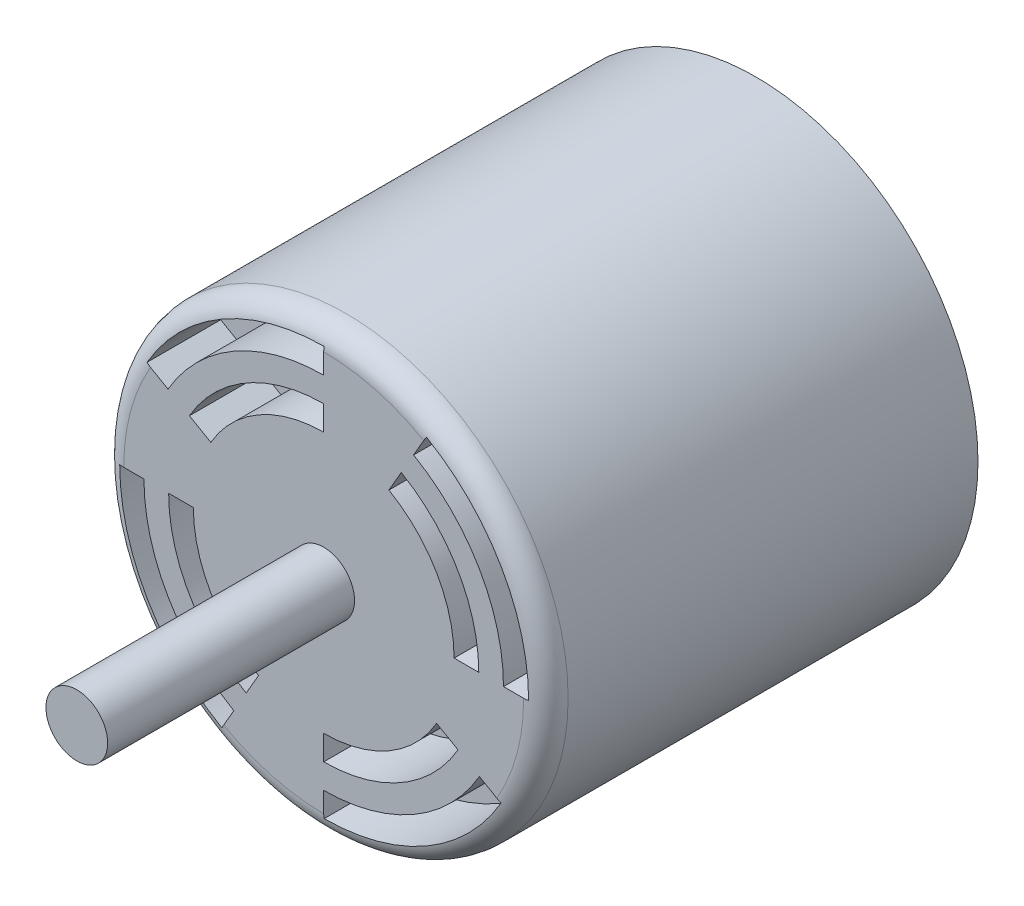
SolidWorks part; units mm, degrees
ref_plane "Front Plane" through (0, 0, 0) normal (0, 0, 1) x (1, 0, 0)
ref_plane "Top Plane" through (0, 0, 0) normal (0, 1, 0) x (1, 0, 0)
ref_plane "Right Plane" through (0, 0, 0) normal (1, 0, 0) x (0, 0, -1)
sketch "Sketch1" plane through (0, 0, 0) normal (0, 0, 1) x (1, 0, 0)
  circle A0 centre (0, 0) radius 22.86
  dimension "D1" = 45.72
extrude "Boss-Extrude1" add sketch "Sketch1" along normal blind 44.45
sketch "Sketch2" plane through (0, 0, 44.45) normal (0, 0, 1) x (1, 0, 0)
  circle A0 centre (0, 0) radius 3.175
  dimension "D1" = 6.35
extrude "Boss-Extrude2" add sketch "Sketch2" along normal blind 25.4
sketch "Sketch3" plane through (0, 0, 44.45) normal (0, 0, 1) x (1, 0, 0)
  line L0 (13.4134, 0) -> (15.9534, 0)
  line L1 (6.7067, 11.6164) -> (7.9767, 13.8161)
  line L2 (9.2467, 16.0158) -> (10.5167, 18.2155)
  line L3 (18.4934, 0) -> (21.0334, 0)
  line L4 (11.6164, -6.7067) -> (13.8161, -7.9767)
  line L5 (16.0158, -9.2467) -> (18.2155, -10.5167)
  line L6 (0, -18.4934) -> (0, -21.0334)
  line L7 (0, -13.4134) -> (0, -15.9534)
  line L8 (-6.7067, -11.6164) -> (-7.9767, -13.8161)
  line L9 (-9.2467, -16.0158) -> (-10.5167, -18.2155)
  line L10 (-18.4934, 0) -> (-21.0334, 0)
  line L11 (-13.4134, 0) -> (-15.9534, 0)
  line L12 (-11.6164, 6.7067) -> (-13.8161, 7.9767)
  line L13 (-16.0158, 9.2467) -> (-18.2155, 10.5167)
  line L14 (0, 18.4934) -> (0, 21.0334)
  line L15 (0, 13.4134) -> (0, 15.9534)
  arc A0 (13.4134, 0) -> (6.7067, 11.6164) centre (0, 0) ccw
  arc A1 (15.9534, 0) -> (7.9767, 13.8161) centre (0, 0) ccw
  arc A2 (21.0334, 0) -> (10.5167, 18.2155) centre (0, 0) ccw
  arc A3 (18.4934, 0) -> (9.2467, 16.0158) centre (0, 0) ccw
  circle A4 centre (0, 0) radius 21.0334 construction
  circle A5 centre (0, 0) radius 18.4934 construction
  circle A6 centre (0, 0) radius 15.9534 construction
  circle A7 centre (0, 0) radius 13.4134 construction
  arc A8 (0, -13.4134) -> (11.6164, -6.7067) centre (0, 0) ccw
  arc A9 (0, -15.9534) -> (13.8161, -7.9767) centre (0, 0) ccw
  arc A10 (0, -18.4934) -> (16.0158, -9.2467) centre (0, 0) ccw
  arc A11 (0, -21.0334) -> (18.2155, -10.5167) centre (0, 0) ccw
  arc A12 (-13.4134, 0) -> (-6.7067, -11.6164) centre (0, 0) ccw
  arc A13 (-15.9534, 0) -> (-7.9767, -13.8161) centre (0, 0) ccw
  arc A14 (-18.4934, 0) -> (-9.2467, -16.0158) centre (0, 0) ccw
  arc A15 (-21.0334, 0) -> (-10.5167, -18.2155) centre (0, 0) ccw
  arc A16 (0, 13.4134) -> (-11.6164, 6.7067) centre (0, 0) ccw
  arc A17 (0, 15.9534) -> (-13.8161, 7.9767) centre (0, 0) ccw
  arc A18 (0, 18.4934) -> (-16.0158, 9.2467) centre (0, 0) ccw
  arc A19 (0, 21.0334) -> (-18.2155, 10.5167) centre (0, 0) ccw
  point P44 (0, 0)
  dimension "D1" = 26.8269
  dimension "D5" = 60
  dimension "D2" = 2.54
  dimension "D3" = 7.62
  dimension "D4" = 5.08
  dimension "D6" = 4
extrude "Cut-Extrude1" cut sketch "Sketch3" against normal blind 7.62
fillet "Fillet1" radius 2.286 1 edges at (22.86, 0, 44.45)
sketch "Sketch4" plane through (0, 0, 0) normal (0, 0, -1) x (-1, 0, 0)
  circle A0 centre (0, 0) radius 2.54
  dimension "D1" = 5.08
extrude "Boss-Extrude3" add sketch "Sketch4" along normal blind 6.35
